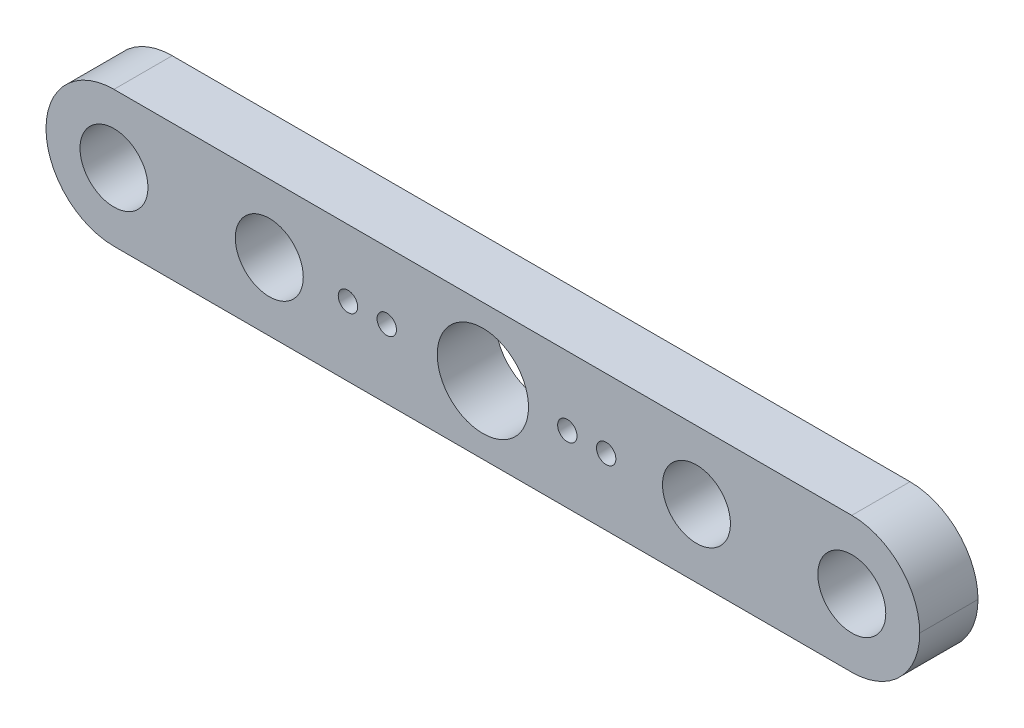
SolidWorks part; units mm, degrees
ref_plane "Front Plane" through (0, 0, 0) normal (0, 0, 1) x (1, 0, 0)
ref_plane "Top Plane" through (0, 0, 0) normal (0, 1, 0) x (1, 0, 0)
ref_plane "Right Plane" through (0, 0, 0) normal (1, 0, 0) x (0, 0, -1)
sketch "Sketch1" plane through (0, 0, 0) normal (0, 0, 1) x (1, 0, 0)
  line L1 (0, 0) -> (-68.3277, 0)
  line L2 (0, 0) -> (0, 52.6864)
  line L3 (0, 52.6864) -> (-68.3277, 52.6864)
  line L4 (-68.3277, 0) -> (-68.3277, 52.6864)
extrude "Boss-Extrude1" add sketch "Sketch1" along normal blind 3
sketch "Sketch2" plane through (0, 0, 0) normal (0, 0, -1) x (-1, 0, 0)
  line L0 (34.7543, 32.2337) -> (0, 32.2337)
  line L1 (68.3277, 0) -> (34.7543, 0)
  line L2 (68.3277, 0) -> (68.3277, 52.6864)
  line L3 (68.3277, 52.6864) -> (34.7543, 52.6864)
  line L4 (34.7543, 15.2724) -> (34.7543, 32.2337)
  line L5 (0, 0) -> (0, 52.6864) construction
  line L6 (34.7543, 15.2724) -> (0, 15.2724)
  line L7 (0, 15.2724) -> (0, 0)
  line L8 (0, 0) -> (34.7543, 0)
  line L9 (0, 52.6864) -> (68.3277, 52.6864) construction
  line L10 (0, 32.2337) -> (0, 52.6864)
  line L11 (0, 52.6864) -> (34.7543, 52.6864)
extrude "Cut-Extrude1" cut sketch "Sketch2" against normal blind 100
sketch "Sketch4" plane through (-34.7543, 0, 0) normal (-1, 0, 0) x (0, 0, 1)
  line L1 (0, 32.2337) -> (3, 32.2337)
  line L2 (0, 32.2337) -> (0, 15.2724)
  line L3 (0, 15.2724) -> (3, 15.2724)
  line L4 (3, 32.2337) -> (3, 15.2724)
extrude "Boss-Extrude2" add sketch "Sketch4" along normal blind 4
sketch "Sketch5" plane through (0, 0, 0) normal (0, 0, -1) x (-1, 0, 0)
  line L0 (38.7543, 15.2724) -> (0, 15.2724) construction
  line L1 (38.7543, 32.2337) -> (35.7543, 32.2337)
  line L2 (38.7543, 32.2337) -> (38.7543, 15.2724)
  line L3 (38.7543, 15.2724) -> (35.7543, 15.2724)
  line L4 (35.7543, 32.2337) -> (35.7543, 15.2724)
  dimension "D1" = 3
extrude "Boss-Extrude3" add sketch "Sketch5" along normal offset from surface (39.5 mm away) 4
sketch "Sketch6" plane through (-35.7543, 0, 0) normal (1, 0, 0) x (0, 0, -1)
  line L0 (39.5, 15.2724) -> (0, 15.2724) construction
  line L1 (39.5, 32.2337) -> (36.5, 32.2337)
  line L2 (39.5, 32.2337) -> (39.5, 15.2724)
  line L3 (39.5, 15.2724) -> (36.5, 15.2724)
  line L4 (36.5, 32.2337) -> (36.5, 15.2724)
  dimension "D1" = 3
extrude "Boss-Extrude4" add sketch "Sketch6" along normal up to surface (35.7543 mm away) up to face at (0, 23.753, 1.5)
fillet "Fillet1" radius 7.5 1 edges at (0, 15.2724, 1.5)
fillet "Fillet2" radius 7.5 1 edges at (0, 32.2337, 1.5)
fillet "Fillet3" radius 7.5 1 edges at (0, 32.2337, -38)
fillet "Fillet4" radius 7.5 1 edges at (0, 15.2724, -38)
sketch "Sketch7" plane through (0, 0, 0) normal (0, 0, -1) x (-1, 0, 0)
  circle A0 centre (15.7855, 30.5158) radius 0.5
  circle A1 centre (15.7855, 30.5158) radius 0.5 construction
  circle A2 centre (15.8056, 28.5159) radius 0.5
  circle A3 centre (15.8056, 28.5159) radius 0.5 construction
  circle A4 centre (20.799, 24.2159) radius 0.5
  circle A5 centre (20.799, 24.2159) radius 0.5 construction
  circle A6 centre (22.7989, 24.236) radius 0.5
  circle A7 centre (22.7989, 24.236) radius 0.5 construction
  circle A8 centre (11.4995, 24.1225) radius 0.5
  circle A9 centre (9.4996, 24.1024) radius 0.5
  circle A10 centre (15.8955, 19.5664) radius 0.5
  circle A11 centre (15.9156, 17.5665) radius 0.5
  circle A12 centre (15.9156, 17.5665) radius 0.5 construction
  circle A13 centre (15.8955, 19.5664) radius 0.5 construction
  circle A14 centre (11.4995, 24.1225) radius 0.5 construction
  circle A15 centre (9.4996, 24.1024) radius 0.5 construction
sketch "Sketch9" plane through (-38.7543, 0, 0) normal (-1, 0, 0) x (0, 0, 1)
  circle A0 centre (-23.1492, 24.2837) radius 0.5
  circle A1 centre (-18.7992, 19.6837) radius 0.5
  circle A2 centre (-13.8492, 24.2837) radius 0.5
  circle A3 centre (-18.7992, 28.6337) radius 0.5
  circle A4 centre (-18.7992, 30.6337) radius 0.5
  circle A5 centre (-18.7992, 17.6837) radius 0.5
  circle A6 centre (-11.8492, 24.2837) radius 0.5
  circle A7 centre (-25.1492, 24.2837) radius 0.5
extrude "Cut-Extrude5" cut sketch "Sketch9" against normal blind 14 contours A2 | A6 | A1 | A5 | A0 | A7 | A4 | A3
extrude "Cut-Extrude6" cut sketch "Sketch7" against normal blind 14
sketch "Sketch10" plane through (-38.7543, 0, 0) normal (-1, 0, 0) x (0, 0, 1)
  circle A0 centre (-18.7992, 24.2837) radius 2.35
  circle A1 centre (-18.7992, 24.2837) radius 2.35 construction
extrude "Cut-Extrude7" cut sketch "Sketch10" against normal blind 10
sketch "Sketch11" plane through (0, 0, 0) normal (0, 0, -1) x (-1, 0, 0)
  circle A0 centre (15.8493, 24.1662) radius 2.35
  circle A1 centre (15.8493, 24.1662) radius 2.35 construction
extrude "Cut-Extrude8" cut sketch "Sketch11" against normal blind 10
sketch "Sketch12" plane through (0, 0, -36.5) normal (0, 0, 1) x (1, 0, 0)
  circle A0 centre (-15.8493, 24.1662) radius 1.5
  circle A1 centre (-15.8493, 24.1662) radius 1.5 construction
extrude "Cut-Extrude9" cut sketch "Sketch12" against normal blind 10
sketch "草圖2" plane through (-35.7543, 0, 0) normal (1, 0, 0) x (0, 0, -1)
  line L1 (4.5004, 39.7761) -> (43.0412, 39.7761)
  line L2 (4.5004, 39.7761) -> (4.5004, 9.0896)
  line L3 (4.5004, 9.0896) -> (43.0412, 9.0896)
  line L4 (43.0412, 39.7761) -> (43.0412, 9.0896)
extrude "除料-伸長4" cut sketch "草圖2" against normal through all and the other way through all
sketch "草圖1" plane through (0, 0, 3) normal (0, 0, 1) x (1, 0, 0)
  line L1 (-30.8493, 27.6662) -> (-0.8493, 27.6662)
  line L2 (-30.8493, 27.6662) -> (-30.8493, 20.6662)
  line L3 (-30.8493, 20.6662) -> (-0.8493, 20.6662)
  line L4 (-0.8493, 27.6662) -> (-0.8493, 20.6662)
  line L5 (-46.8759, 38.3247) -> (11.5255, 38.3247)
  line L6 (-46.8759, 38.3247) -> (-46.8759, 10.1758)
  line L7 (-46.8759, 10.1758) -> (11.5255, 10.1758)
  line L8 (11.5255, 38.3247) -> (11.5255, 10.1758)
  circle A1 centre (-26.8493, 24.1662) radius 1.75
  circle A2 centre (-4.8493, 24.1662) radius 1.75
  circle M12 centre (-15.7855, 30.5158) radius 0.5
  circle M13 centre (-15.9156, 17.5665) radius 0.5
  circle M14 centre (-15.8955, 19.5664) radius 0.5
  circle M16 centre (-15.8056, 28.5159) radius 0.5
  line M20 (0, 22.7724) -> (0, 24.7337)
  arc M21 (0, 24.7337) -> (-7.5, 32.2337) centre (-7.5, 24.7337) ccw
  line M22 (-7.5, 32.2337) -> (-38.7543, 32.2337)
  line M23 (-38.7543, 32.2337) -> (-38.7543, 15.2724)
  line M24 (-38.7543, 15.2724) -> (-7.5, 15.2724)
  arc M25 (-7.5, 15.2724) -> (0, 22.7724) centre (-7.5, 22.7724) ccw
  dimension "D5" = 3.5
  dimension "D6" = 3.5
  dimension "D8" = 4
  dimension "D7" = 4
  dimension "D9" = 3.5
extrude "除料-伸長7" cut sketch "草圖1" against normal through all contours L8 L5 L6 L7 M20 M25 M24 M23 M22 M21 | A1 | A2 | L1 L4 L3 L2 M25 M20 M21 M22 M23 M24 M13 M16 M14 M12
sketch "草圖3" plane through (0, 0, 3) normal (0, 0, 1) x (1, 0, 0)
  line L0 (-30.8493, 20.6662) -> (-0.8493, 20.6662) construction
  line L1 (-30.8493, 27.6662) -> (-38.3493, 27.6662)
  line L2 (-30.8493, 27.6662) -> (-30.8493, 20.6662)
  line L3 (-30.8493, 20.6662) -> (-38.3493, 20.6662)
  line L4 (-38.3493, 27.6662) -> (-38.3493, 20.6662)
  line L5 (-0.8493, 27.6662) -> (6.6507, 27.6662)
  line L6 (-0.8493, 27.6662) -> (-0.8493, 20.6662)
  line L7 (-0.8493, 20.6662) -> (6.6507, 20.6662)
  line L8 (6.6507, 27.6662) -> (6.6507, 20.6662)
  circle A2 centre (-34.8493, 24.1662) radius 1.75
  circle A3 centre (3.1507, 24.1662) radius 1.75
  point P20 (0, 0)
  dimension "D1" = 7.5
extrude "填料-伸長1" add sketch "草圖3" against normal through all
fillet "圓角2" radius 3.5 4 edges at (6.6507, 20.6662, 1.5) (6.6507, 27.6662, 1.5) (-38.3493, 20.6662, 1.5) (-38.3493, 27.6662, 1.5)
